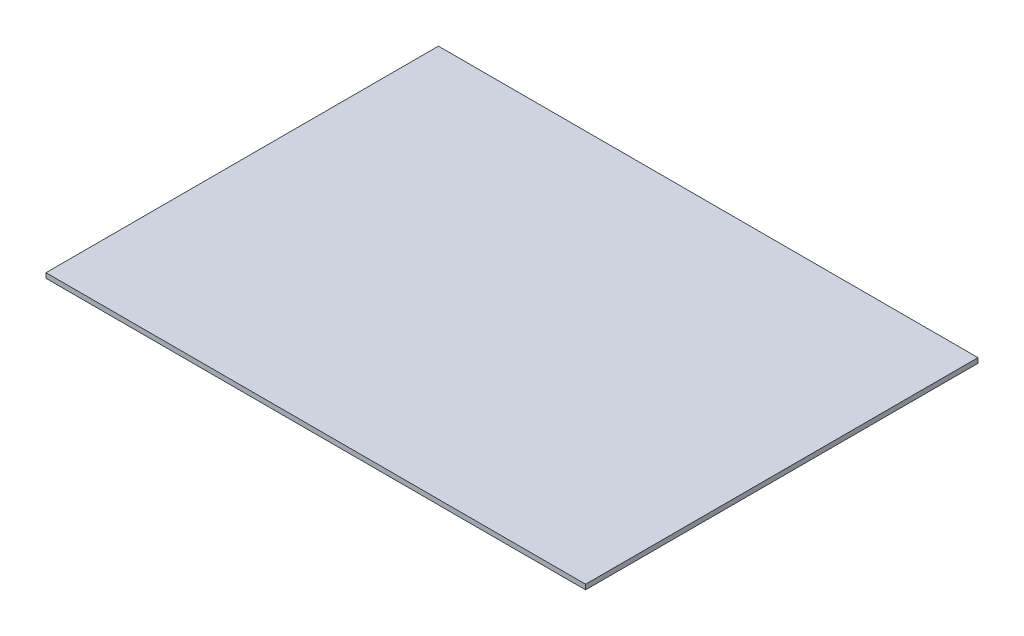
SolidWorks part; units mm, degrees
ref_plane "正面" through (0, 0, 0) normal (0, 0, 1) x (1, 0, 0)
ref_plane "平面" through (0, 0, 0) normal (0, 1, 0) x (1, 0, 0)
ref_plane "右側面" through (0, 0, 0) normal (1, 0, 0) x (0, 0, -1)
sketch "ｽｹｯﾁ1" plane through (0, 0, 0) normal (0, 1, 0) x (1, 0, 0)
  line L1 (-275, 200) -> (275, 200)
  line L2 (-275, 200) -> (-275, -200)
  line L3 (-275, -200) -> (275, -200)
  line L4 (275, 200) -> (275, -200)
  line L5 (-275, 200) -> (275, -200) construction
  line L6 (-275, -200) -> (275, 200) construction
  point P0 (0, 0)
  dimension "D1" = 400
  dimension "D2" = 550
extrude "ﾎﾞｽ - 押し出し1" add sketch "ｽｹｯﾁ1" along normal blind 5
